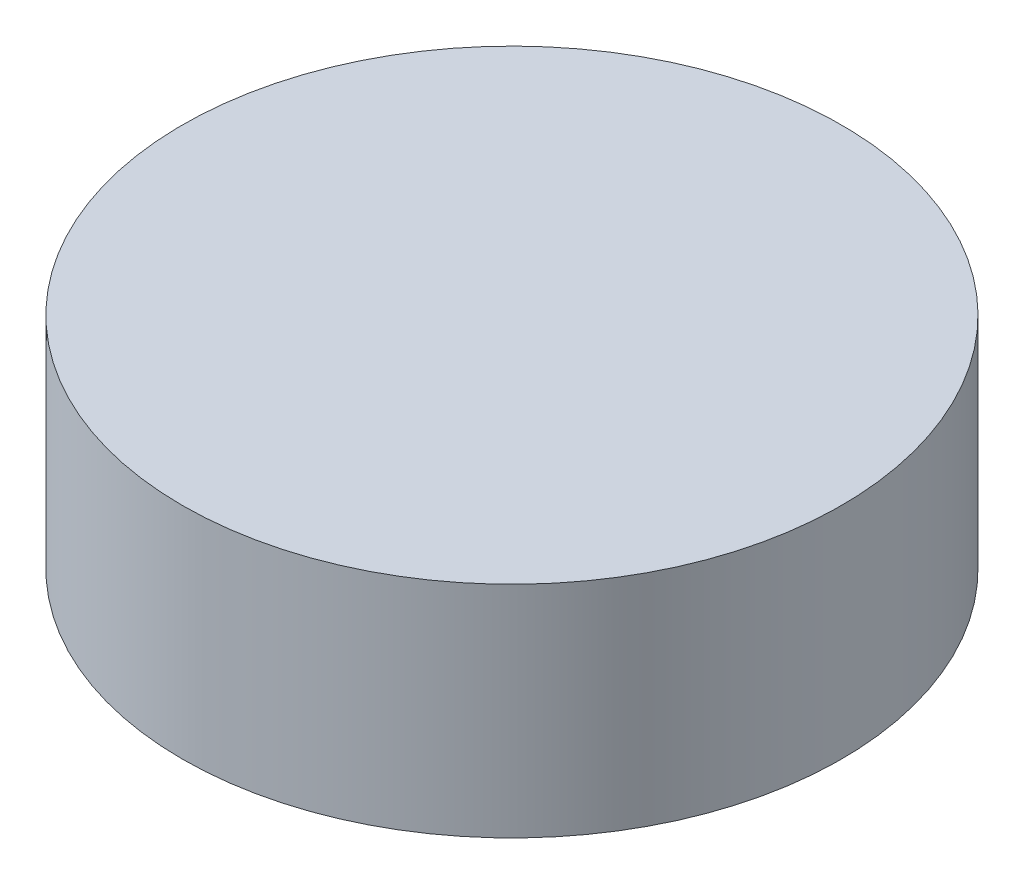
SolidWorks part; units mm, degrees
ref_plane "前视基准面" through (0, 0, 0) normal (0, 0, 1) x (1, 0, 0)
ref_plane "上视基准面" through (0, 0, 0) normal (0, 1, 0) x (1, 0, 0)
ref_plane "右视基准面" through (0, 0, 0) normal (1, 0, 0) x (0, 0, -1)
other "Configuration Table"
sketch "草图1" plane through (0, 0, 0) normal (0, 1, 0) x (1, 0, 0)
  circle A0 centre (0, 0) radius 120
extrude "凸台-拉伸1" add sketch "草图1" along normal blind 80
